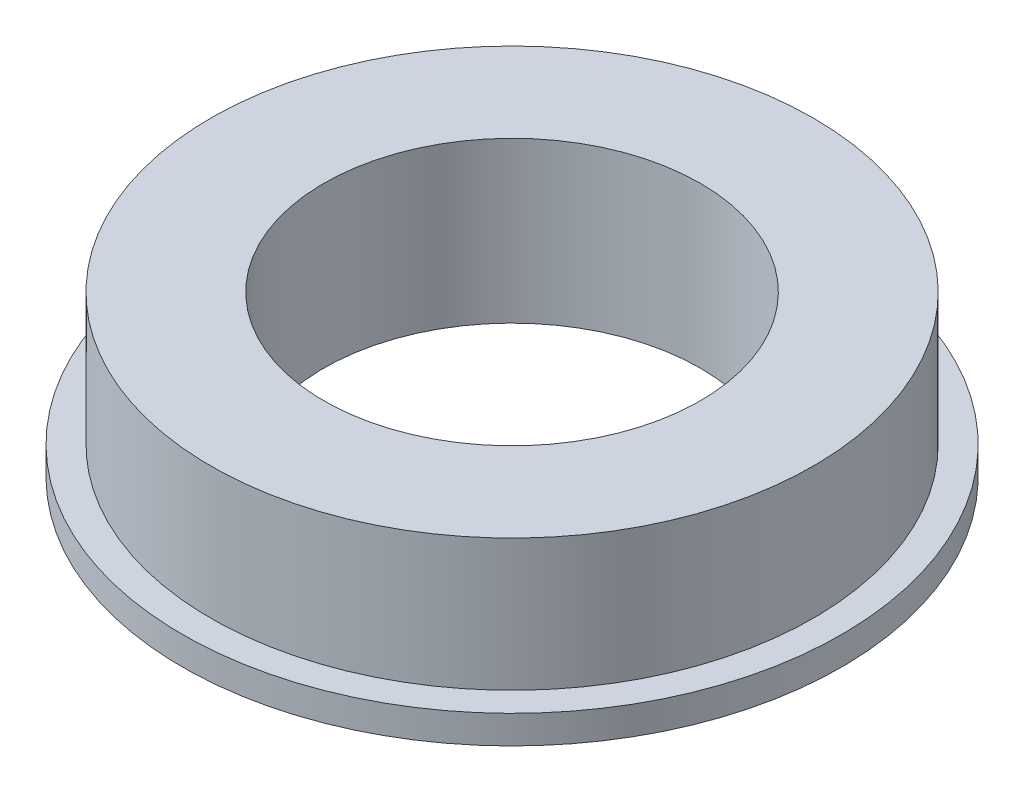
SolidWorks part; units mm, degrees
ref_plane "前视基准面" through (0, 0, 0) normal (0, 0, 1) x (1, 0, 0)
ref_plane "上视基准面" through (0, 0, 0) normal (0, 1, 0) x (1, 0, 0)
ref_plane "右视基准面" through (0, 0, 0) normal (1, 0, 0) x (0, 0, -1)
sketch "草图1" plane through (0, 0, 0) normal (0, 0, 1) x (1, 0, 0)
  line L0 (16, 1.5) -> (16, 8.5)
  line L1 (16, 8.5) -> (10, 8.5)
  line L2 (10, 8.5) -> (10, 0)
  line L3 (10, 0) -> (17.5, 0)
  line L4 (17.5, 0) -> (17.5, 1.5)
  line L5 (17.5, 1.5) -> (16, 1.5)
  line L6 (0, 7) -> (0, 0) construction
  dimension "D1" = 1.5
  dimension "D2" = 6
  dimension "D3" = 7
revolve "旋转1" add sketch "草图1" angle 360 about L6 reverse direction yes
